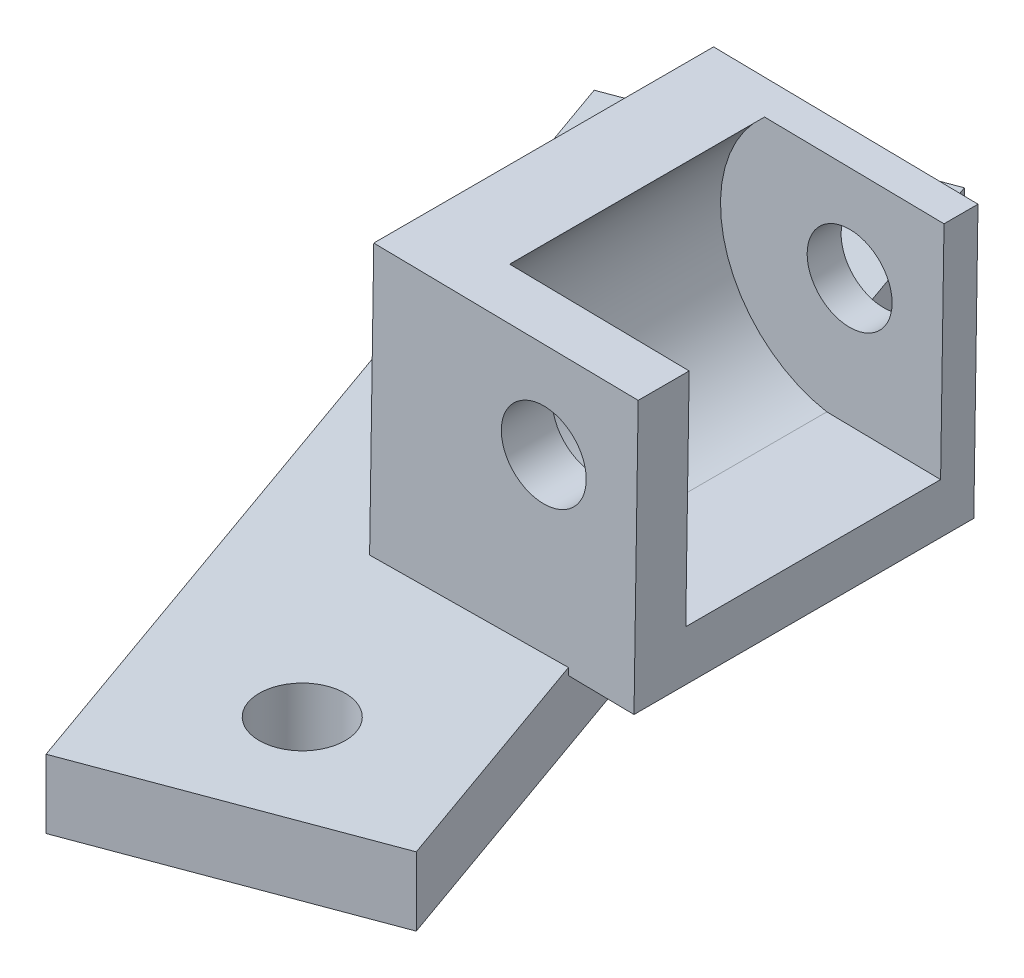
SolidWorks part; units mm, degrees
ref_plane "Front Plane" through (0, 0, 0) normal (0, 0, 1) x (1, 0, 0)
ref_plane "Top Plane" through (0, 0, 0) normal (0, 1, 0) x (1, 0, 0)
ref_plane "Right Plane" through (0, 0, 0) normal (1, 0, 0) x (0, 0, -1)
sketch "Sketch1" plane through (0, 0, 0) normal (0, 0, 1) x (1, 0, 0)
  line L0 (-620.8374, 110.7203) -> (-621.1503, 90.2249)
  line L1 (-604.7125, 110.4741) -> (-634.2525, 110.9251) construction
  line L2 (-621.1503, 90.2249) -> (-640.9147, 90.5267)
  line L3 (-640.9147, 90.5267) -> (-640.6018, 111.0221)
  line L4 (-640.6018, 111.0221) -> (-620.8374, 110.7203)
  line L5 (-606.4491, 93.8109) -> (-629.5989, 94.1643) construction
  line L6 (-606.4491, 93.8109) -> (-629.5989, 94.1643)
  arc A0 (-634.2525, 110.9251) -> (-634.4712, 96.6012) centre (-627.8931, 103.6644) ccw construction
  arc A1 (-634.4712, 96.6012) -> (-629.5989, 94.1643) centre (-627.8931, 103.6644) ccw construction
  arc A2 (-634.2525, 110.9251) -> (-634.4712, 96.6012) centre (-627.8931, 103.6644) ccw
  arc A3 (-634.4712, 96.6012) -> (-629.5989, 94.1643) centre (-627.8931, 103.6644) ccw
  dimension "D1" = 3.81
  dimension "D2" = 6.35
  dimension "D3" = 19.7667
extrude "Boss-Extrude1" add sketch "Sketch1" against normal blind 21.59 contours A3 A2 L4 L3 L2 L0 L6 region at (-621.4085, 92.1341, 0)
sketch "Sketch2" plane through (0, 0, -19.05) normal (0, 0, -1) x (-1, 0, 0)
  line L0 (621.0921, 94.0345) -> (620.8374, 110.7203)
  line L1 (604.6203, 110.4727) -> (634.2525, 110.9251) construction
  line L2 (620.8374, 110.7203) -> (634.2525, 110.9251)
  line L3 (621.0921, 94.0345) -> (629.5989, 94.1643) construction
  line L4 (621.0921, 94.0345) -> (629.5989, 94.1643)
  line L5 (621.0921, 94.0345) -> (629.5989, 94.1643)
  circle A0 centre (627.8931, 103.6644) radius 3.175 construction
  arc A1 (629.5989, 94.1643) -> (634.2525, 110.9251) centre (627.8931, 103.6644) ccw construction
  circle A2 centre (627.8931, 103.6644) radius 3.175
  arc A3 (629.5989, 94.1643) -> (634.2525, 110.9251) centre (627.8931, 103.6644) ccw
  circle M6 centre (627.8931, 103.6644) radius 3.175
  line M7 (604.4767, 96.1432) -> (634.4712, 96.6012)
  arc M8 (634.4712, 96.6012) -> (634.2525, 110.9251) centre (627.8931, 103.6644) ccw
  line M9 (634.2525, 110.9251) -> (604.6203, 110.4727)
extrude "Boss-Extrude3" add sketch "Sketch2" along normal up to surface (2.54 mm away) contours L0 M7 M8 M9 M6 | L4 A3 L0 M7 region at (-626.9307, 95.381, -19.05) region at (-621.1681, 103.5617, -19.05) up to face at (-632.1463, 98.2392, -21.59)
sketch "Sketch3" plane through (0, 0, 0) normal (0, 0, 1) x (1, 0, 0)
  line L0 (-640.6018, 111.0221) -> (-620.8374, 110.7203)
  line L1 (-620.8374, 110.7203) -> (-621.1503, 90.2249)
  line L2 (-621.1503, 90.2249) -> (-640.9147, 90.5267)
  line L3 (-640.9147, 90.5267) -> (-640.6018, 111.0221)
  circle A0 centre (-627.8931, 103.6644) radius 3.175
  dimension "D1" = 6.35
extrude "Boss-Extrude4" add sketch "Sketch3" along normal blind 3.81 contours L3 L0 L1 L2 | A0
ref_plane "Plane1" through (-1.0096, 97.2566, -1.0889) normal (-0.0104, 0.9999, -0.0112) x (0.9999, 0.0104, -0.0001)
sketch "Sketch4" plane through (-1.0096, 97.2566, -1.0889) normal (-0.0104, 0.9999, -0.0112) x (0.9999, 0.0104, -0.0001)
  line L0 (-662.311, 34.3361) -> (-638.8443, -30.104)
  line L5 (-638.8443, -30.104) -> (-618.5576, -22.7163)
  line L6 (-618.5576, -22.7163) -> (-642.0243, 41.7238)
  line L7 (-642.0243, 41.7238) -> (-662.311, 34.3361)
  line L8 (-620.1809, -4.8198) -> (-639.9411, -4.8232) construction
  circle A1 centre (-649.1257, 29.6766) radius 3.175
  circle A2 centre (-631.7429, -18.0568) radius 3.175
  dimension "D7" = 10.795
  dimension "D9" = 6.35
  dimension "D10" = 6.35
  dimension "D6" = 8.89
  dimension "D1" = 21.59
  dimension "D2" = 7.62
  dimension "D3" = 110
  dimension "D4" = 68.58
  dimension "D5" = 24.13
  dimension "D8" = 10.795
  dimension "D11" = 8.89
extrude "Boss-Extrude5" add sketch "Sketch4" against normal blind 5.08
